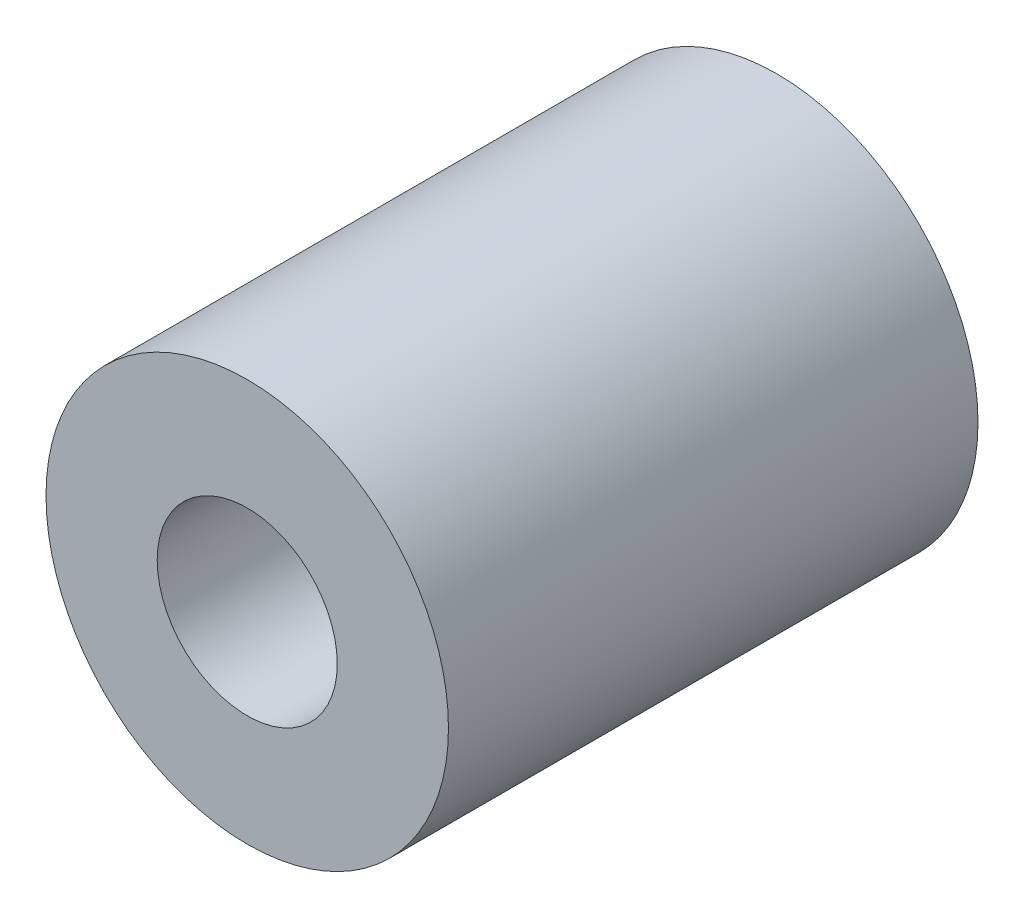
SolidWorks part; units mm, degrees
ref_plane "Front Plane" through (0, 0, 0) normal (0, 0, 1) x (1, 0, 0)
ref_plane "Top Plane" through (0, 0, 0) normal (0, 1, 0) x (1, 0, 0)
ref_plane "Right Plane" through (0, 0, 0) normal (1, 0, 0) x (0, 0, -1)
sketch "Sketch1" plane through (0, 0, 0) normal (0, 0, 1) x (1, 0, 0)
  circle A0 centre (0, 0) radius 9.5
  dimension "D1" = 19
extrude "Boss-Extrude1" add sketch "Sketch1" along normal blind 25 contours A0
extrude "Boss-Extrude2" add sketch "Sketch1<3>" along normal blind 25
sketch "Sketch1<3>" plane through (0, 0, 0) normal (0, 0, 1) x (1, 0, 0) same geometry as "Sketch1"
sketch "Sketch2" plane through (0, 0, 25) normal (0, 0, 1) x (1, 0, 0)
  circle A0 centre (0, 0) radius 4.25
  dimension "D1" = 8.5
extrude "Cut-Extrude1" cut sketch "Sketch2" against normal blind 25
